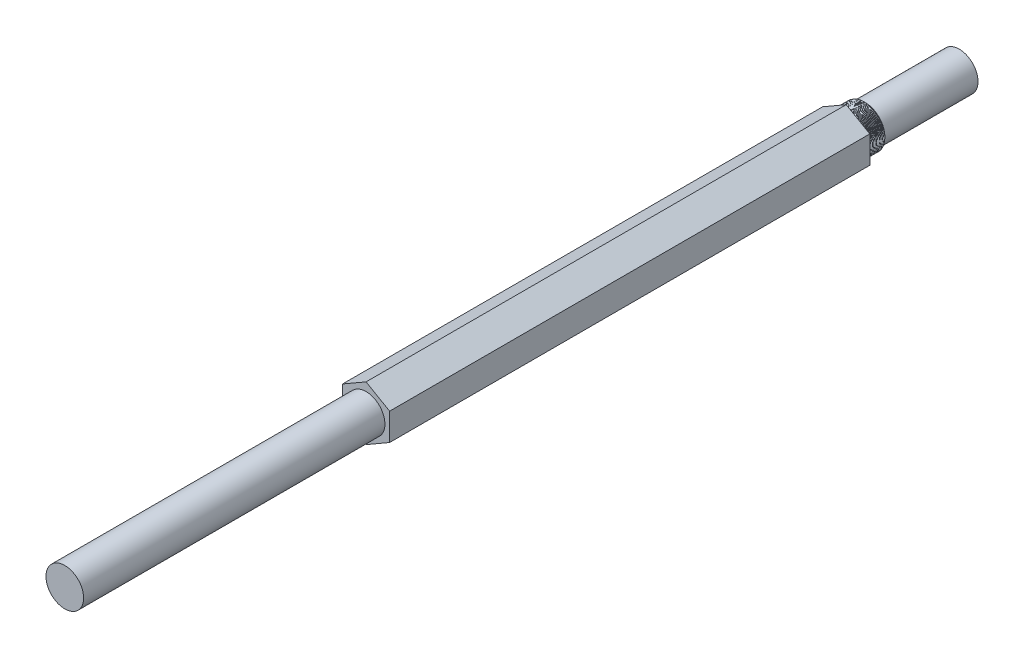
SolidWorks part; units mm, degrees
ref_plane "Front Plane" through (0, 0, 0) normal (0, 0, 1) x (1, 0, 0)
ref_plane "Top Plane" through (0, 0, 0) normal (0, 1, 0) x (1, 0, 0)
ref_plane "Right Plane" through (0, 0, 0) normal (1, 0, 0) x (0, 0, -1)
sketch "Sketch1" plane through (0, 0, 0) normal (0, 0, 1) x (1, 0, 0)
  line L1 (0, 28.8675) -> (-25, 14.4338)
  line L2 (-25, 14.4338) -> (-25, -14.4338)
  line L3 (-25, -14.4338) -> (0, -28.8675)
  line L4 (0, -28.8675) -> (25, -14.4338)
  line L5 (25, -14.4338) -> (25, 14.4338)
  line L6 (25, 14.4338) -> (0, 28.8675)
  circle A0 centre (0, 0) radius 25 construction
  dimension "D1" = 50
extrude "Boss-Extrude1" add sketch "Sketch1" along normal blind 950
sketch "Sketch2" plane through (0, 0, 0) normal (0, 0, -1) x (-1, 0, 0)
  circle A0 centre (0, 0) radius 22.5
  circle A1 centre (0, 0) radius 32.775
  dimension "D1" = 45
  dimension "D2" = 65.55
extrude "Cut-Extrude1" cut sketch "Sketch2" against normal blind 120
sketch "Sketch3" plane through (0, 0, 0) normal (0, 0, -1) x (-1, 0, 0)
  circle A0 centre (0, 0) radius 20
  circle A1 centre (0, 0) radius 22.5 construction
  circle A2 centre (0, 0) radius 22.5
  dimension "D1" = 40
extrude "Cut-Extrude2" cut sketch "Sketch3" against normal blind 100
sketch "Sketch4" plane through (0, 0, 100) normal (0, 0, -1) x (-1, 0, 0)
  circle A0 centre (0, 0) radius 22.5
curve "Helix/Spiral1" pitch 1.25 height 20 radius 22.5 centre (0, 0, 100) axis (0, 0, 1) start towards (0, 1, 0)
chamfer "Chamfer1" distance 1.5 angle 45 1 edges at (-22.5, 0, 100)
sketch "Sketch5" plane through (0, 0, 0) normal (1, 0, 0) x (0, 0, -1)
  line L0 (-100, 20) -> (-100, 38.882) construction
  line L1 (-100, -20) -> (-100, 20) construction
  line L2 (-100, -21) -> (-100, 21) construction
  line L3 (-108.1466, 22.55) -> (-84.1127, 22.55) construction
  line L4 (-101.5, 22.5) -> (-120, 22.5) construction
  line L6 (-99.84, 21.5771) -> (-99.4333, 22.2815)
  line L7 (-100.7217, 22.55) -> (-99.2783, 22.55)
  line L10 (-99.4333, 22.2815) -> (-99.1233, 22.2815)
  line L11 (-100.16, 21.5771) -> (-99.84, 21.5771)
  line L12 (-99.2783, 22.55) -> (-99.1233, 22.55)
  line L13 (-99.1233, 22.55) -> (-99.1233, 22.2815)
  line L14 (-100.16, 21.5771) -> (-100.5667, 22.2815)
  line L15 (-100.5667, 22.2815) -> (-100.8767, 22.2815)
  line L16 (-100.8767, 22.55) -> (-100.8767, 22.2815)
  line L17 (-100.7217, 22.55) -> (-100.8767, 22.55)
  point P14 (-100, 21.5771)
  point P22 (-100, 22.55)
  dimension "D1" = 0.05
  dimension "D5" = 0.31
  dimension "D6" = 0.16
sweep "Cut-Sweep1" cut profiles "Sketch5" path "Helix/Spiral1" align with end faces yes
sketch "Sketch6" plane through (0, 0, 950) normal (0, 0, 1) x (1, 0, 0)
  circle A0 centre (0, 0) radius 20
  circle A1 centre (0, 0) radius 44.3355
  dimension "D1" = 40
extrude "Cut-Extrude3" cut sketch "Sketch6" against normal blind 320
